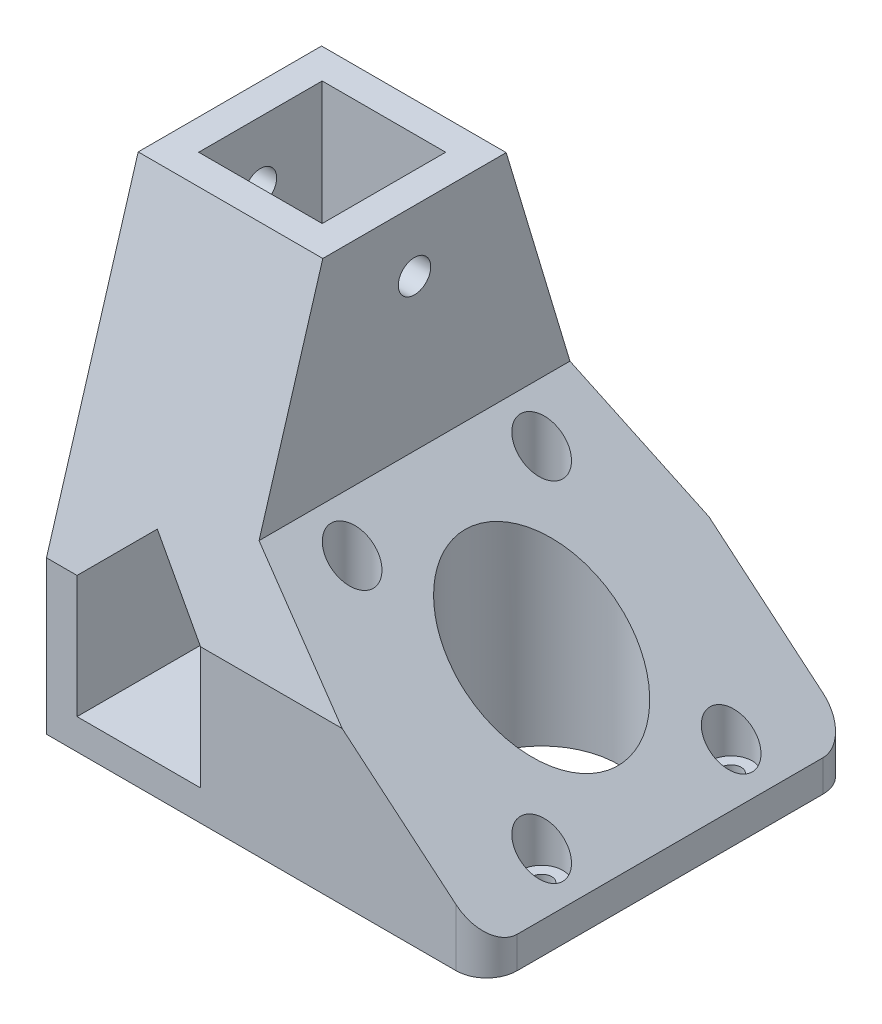
SolidWorks part; units mm, degrees
ref_plane "Front Plane" through (0, 0, 0) normal (0, 0, 1) x (1, 0, 0)
ref_plane "Top Plane" through (0, 0, 0) normal (0, 1, 0) x (1, 0, 0)
ref_plane "Right Plane" through (0, 0, 0) normal (1, 0, 0) x (0, 0, -1)
sketch "Sketch1" plane through (0, 0, 0) normal (0, 1, 0) x (1, 0, 0)
  line L1 (0, 0) -> (72, 0)
  line L2 (0, 0) -> (0, 60)
  line L3 (0, 60) -> (72, 60)
  line L4 (72, 0) -> (72, 60)
  dimension "D1" = 72
  dimension "D2" = 60
extrude "Boss-Extrude1" add sketch "Sketch1" along normal blind 5
sketch "Sketch2" plane through (0, 5, 0) normal (0, 1, 0) x (1, 0, 0)
  line L0 (0, 0) -> (72, 0) construction
  line L1 (0, 60) -> (5, 60)
  line L2 (0, 60) -> (0, 0)
  line L3 (0, 0) -> (5, 0)
  line L4 (5, 60) -> (5, 0)
  dimension "D1" = 5
extrude "Boss-Extrude2" add sketch "Sketch2" along normal blind 70
sketch "Sketch3" plane through (0, 5, 0) normal (0, 1, 0) x (1, 0, 0)
  line L0 (72, 60) -> (5, 60) construction
  line L1 (25.2, 60) -> (30.2, 60)
  line L2 (25.2, 60) -> (25.2, 0)
  line L3 (25.2, 0) -> (30.2, 0)
  line L4 (30.2, 60) -> (30.2, 0)
  line L5 (5, 0) -> (72, 0) construction
  line L6 (5, 0) -> (5, 60) construction
  dimension "D1" = 5
  dimension "D2" = 20.2
extrude "Boss-Extrude3" add sketch "Sketch3" along normal blind 70
sketch "Sketch11" plane through (0, 0, -60) normal (0, 0, -1) x (-1, 0, 0)
  line L0 (-25.2, 25) -> (-15.1, 35.1)
  line L1 (-25.2, 75) -> (-25.2, 5) construction
  line L2 (-15.1, 35.1) -> (-5, 25)
  line L3 (-5, 75) -> (-5, 5) construction
  line L4 (-5, 25) -> (-5, 75)
  line L5 (-5, 75) -> (-25.2, 75)
  line L6 (-25.2, 75) -> (-25.2, 25)
  dimension "D1" = 50
  dimension "D2" = 50
  dimension "D3" = 45
  dimension "D4" = 45
extrude "Boss-Extrude4" add sketch "Sketch11" against normal up to surface (60 mm away) up to face at (26.48, 32, 0)
chamfer "Chamfer1" distance 42 angle 40 1 edges at (30.2, 5, -30) first distance on face at (51.1, 5, -30)
chamfer "Chamfer2" distance 50 angle 16.7 2 edges at (15.1, 75, -60) (15.1, 75, 0) first distance on face at (15.1, 19.02, -60) first distance on face at (15.1, 19.02, 0)
sketch "Sketch12" plane through (0, 75, 0) normal (0, 1, 0) x (1, 0, 0)
  line L0 (0, 30) -> (30.2, 30) construction
  line L1 (5, 40.1) -> (25.2, 40.1)
  line L2 (5, 40.1) -> (5, 19.9)
  line L3 (5, 19.9) -> (25.2, 19.9)
  line L4 (25.2, 40.1) -> (25.2, 19.9)
  line L5 (5, 40.1) -> (25.2, 19.9) construction
  line L6 (5, 19.9) -> (25.2, 40.1) construction
  line L8 (30.2, 4.5729) -> (30.2, 55.4271) construction
  line L9 (0, 44.9993) -> (0, 15.0007) construction
  point P0 (15.1, 30)
  point P5 (0, 30)
  point P8 (15.2, 30)
  point P9 (15.1, 30)
  point P14 (0, 0)
  point P15 (0, 0)
  dimension "D1" = 20.2
  dimension "D2" = 20.2
  dimension "D3" = 5
extrude "Cut-Extrude8" cut sketch "Sketch12" against normal blind 67
sketch "Sketch5" plane through (0, 5, 0) normal (0, 1, 0) x (1, 0, 0)
  line L0 (72, 0) -> (72, 60) construction
  line L1 (5, 0) -> (25.2, 0) construction
  circle A0 centre (51, 30) radius 12.5
  dimension "D1" = 25
  dimension "D2" = 21
  dimension "D3" = 30
extrude "Cut-Extrude1" cut sketch "Sketch5" against normal through all both and the other way through all
sketch "Sketch6" plane through (0, 0, 0) normal (0, -1, 0) x (1, 0, 0)
  line L1 (35.5, -14.5) -> (66.5, -14.5) construction
  line L2 (35.5, -14.5) -> (35.5, -45.5) construction
  line L3 (35.5, -45.5) -> (66.5, -45.5) construction
  line L4 (66.5, -14.5) -> (66.5, -45.5) construction
  line L5 (35.5, -14.5) -> (66.5, -45.5) construction
  line L6 (35.5, -45.5) -> (66.5, -14.5) construction
  circle A0 centre (66.5, -14.5) radius 1.65
  circle A1 centre (66.5, -45.5) radius 1.65
  circle A2 centre (35.5, -45.5) radius 1.65
  circle A3 centre (35.5, -14.5) radius 1.65
  point P0 (51, -30)
  dimension "D3" = 3.3
  dimension "D1" = 31
  dimension "D2" = 31
extrude "Cut-Extrude2" cut sketch "Sketch6" against normal through all
sketch "Sketch7" plane through (0, 5, 0) normal (0, 1, 0) x (1, 0, 0)
  circle A0 centre (66.5, 45.5) radius 3.45
  circle A1 centre (66.5, 14.5) radius 3.45
  circle A2 centre (35.5, 14.5) radius 3.45
  circle A4 centre (35.5, 45.5) radius 3.45
  point P11 (0, 0)
  point P12 (34.5, 45.5)
  dimension "D1" = 6.9
extrude "Cut-Extrude4" cut sketch "Sketch7" along normal through all
sketch "Sketch8" plane through (30.2, 0, 0) normal (1, 0, 0) x (0, 0, -1)
  line L0 (15.0007, 75) -> (44.9993, 75) construction
  line L1 (30, 75) -> (30, 40.2422) construction
  line L2 (4.5729, 40.2422) -> (55.4271, 40.2422) construction
  circle A0 centre (30, 65) radius 2.65
  dimension "D1" = 5.3
  dimension "D2" = 10
extrude "Cut-Extrude5" cut sketch "Sketch8" against normal through all both and the other way through all
sketch "Sketch9" plane through (0, 0, 0) normal (0, -1, 0) x (1, 0, 0)
  line L1 (0, -60) -> (0, 0) construction
  line L2 (0, -30) -> (72, -30) construction
  line L3 (72, 0) -> (72, -60) construction
  circle A0 centre (15, -30) radius 2.65
  dimension "5.3" = 5.3
  dimension "D2" = 15
extrude "Cut-Extrude6" cut sketch "Sketch9" against normal through all both and the other way through all contours A0
fillet "Fillet1" radius 5 2 edges at (72, 2.5839, -60) (72, 2.5839, 0)
sketch "Sketch10" plane through (0, 0, 0) normal (-1, 0, 0) x (0, 0, 1)
  line L0 (-60, 0) -> (0, 0) construction
  line L1 (0, 25) -> (0, 0) construction
  circle A0 centre (-30, 15) radius 2.65
  dimension "D3" = 5.3
  dimension "D1" = 15
  dimension "D2" = 30
extrude "Cut-Extrude7" cut sketch "Sketch10" against normal blind 10
